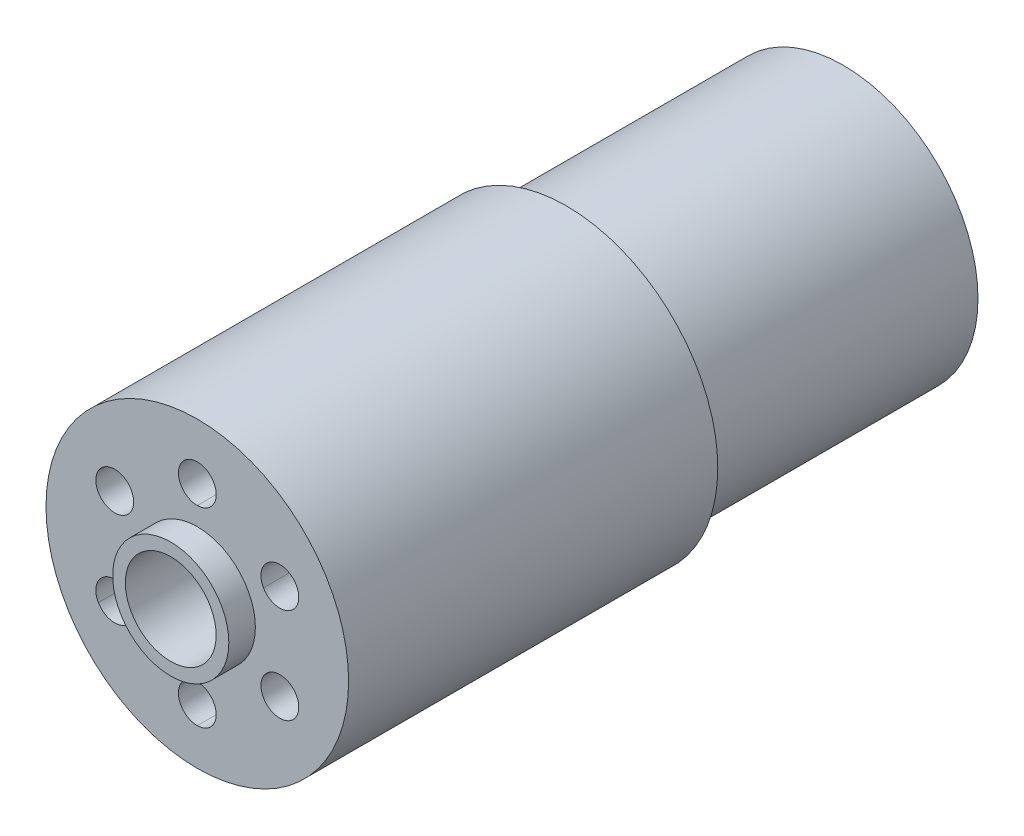
SolidWorks part; units mm, degrees
ref_plane "Front Plane" through (0, 0, 0) normal (0, 0, 1) x (1, 0, 0)
ref_plane "Top Plane" through (0, 0, 0) normal (0, 1, 0) x (1, 0, 0)
ref_plane "Right Plane" through (0, 0, 0) normal (1, 0, 0) x (0, 0, -1)
sketch "Sketch1" plane through (0, 0, 0) normal (0, 0, 1) x (1, 0, 0)
  circle A0 centre (0, 0) radius 25.4
  circle A8 centre (0, 0) radius 9.3953
  point P19 (0, 0)
  dimension "D1" = 50.8
  dimension "D2" = 16.0047
extrude "Boss-Extrude2" add sketch "Sketch1" along normal blind 108.458 contours A0
sketch "Sketch6" plane through (0, 0, 0) normal (0, 0, -1) x (-1, 0, 0)
  circle A0 centre (0, 0) radius 7.62
  circle A1 centre (-13.8581, 8.001) radius 3.175
  circle A2 centre (0, 16.002) radius 3.175
  circle A3 centre (13.8581, 8.001) radius 3.175
  circle A4 centre (13.8581, -8.001) radius 3.175
  circle A5 centre (0, -16.002) radius 3.175
  circle A6 centre (-13.8581, -8.001) radius 3.175
  point P18 (0, 0)
  dimension "D1" = 15.24
  dimension "D2" = 6.35
  dimension "D3" = 16.002
  dimension "D4" = 6
extrude "Cut-Extrude1" cut sketch "Sketch6" against normal blind 108.458
sketch "Sketch7" plane through (0, 0, 0) normal (0, 0, -1) x (-1, 0, 0)
  circle A0 centre (0, 0) radius 22.606
  circle A1 centre (0, 0) radius 25.4 construction
  circle A2 centre (0, 0) radius 25.4
  dimension "D1" = 2.794
extrude "Cut-Extrude2" cut sketch "Sketch7" against normal blind 46.482
sketch "Sketch8" plane through (0, 0, 108.458) normal (0, 0, 1) x (1, 0, 0)
  circle A0 centre (0, 0) radius 7.62
  circle A1 centre (0, 0) radius 9.75
  dimension "D1" = 19.5
  dimension "D2" = 15.24
extrude "Boss-Extrude7" add sketch "Sketch8" along normal blind 4.4577
sketch "Sketch9" plane through (0, 0, 0) normal (0, 0, -1) x (-1, 0, 0)
  circle A0 centre (0, 0) radius 7.62
  circle A1 centre (0, 0) radius 9.75
  dimension "D1" = 19.5
  dimension "D2" = 15.24
extrude "Boss-Extrude8" add sketch "Sketch9" along normal blind 4.4577
sketch "Sketch10" plane through (0, 0, 0) normal (0, 0, -1) x (-1, 0, 0)
  circle A0 centre (0, 16.002) radius 3.175 construction
  circle A1 centre (0, -16.002) radius 3.175 construction
  circle A2 centre (0, 0) radius 19.177 construction
  circle A3 centre (-13.8581, 8.001) radius 3.175 construction
  circle A4 centre (-13.8581, -8.001) radius 3.175 construction
  circle A5 centre (13.8581, -8.001) radius 3.175 construction
  circle A6 centre (0, 0) radius 12.827 construction
  point P0 (0, 19.177)
  point P1 (0, -19.177)
  point P9 (-16.6078, 9.5885)
  point P10 (-16.6078, -9.5885)
  point P13 (16.6078, -9.5885)
  point P16 (16.6078, 9.5885)
  point P20 (0, 12.827)
  point P21 (-10.9777, 6.6349)
  point P22 (-10.9777, -6.6349)
  point P23 (11.1085, -6.4135)
  point P24 (11.1085, 6.4135)
  point P25 (0, -12.827)
sketch "Sketch11" plane through (0, 0, 108.458) normal (0, 0, 1) x (1, 0, 0)
  point P0 (10.9777, 6.6349)
  point P2 (10.9777, -6.6349)
  point P4 (0, -12.827)
  point P6 (-11.1085, -6.4135)
  point P8 (-11.1085, 6.4135)
  point P10 (0, 12.827)
ref_plane "Plane1" through (0, 0, 0) normal (-1, 0, 0) x (0, 0, 1)
ref_plane "Plane3" through (0, 0, 0) normal (-0.5, -0.866, 0) x (-0.866, 0.5, 0)
ref_plane "Plane6" through (0, 0, 0) normal (0.5, -0.866, 0) x (-0.866, -0.5, 0)
split line "Split Line1"
split line "Split Line2"
split line "Split Line3"
ref_axis "Axis1" through (0, 0, 112.9157) along (0, 0, -1)
